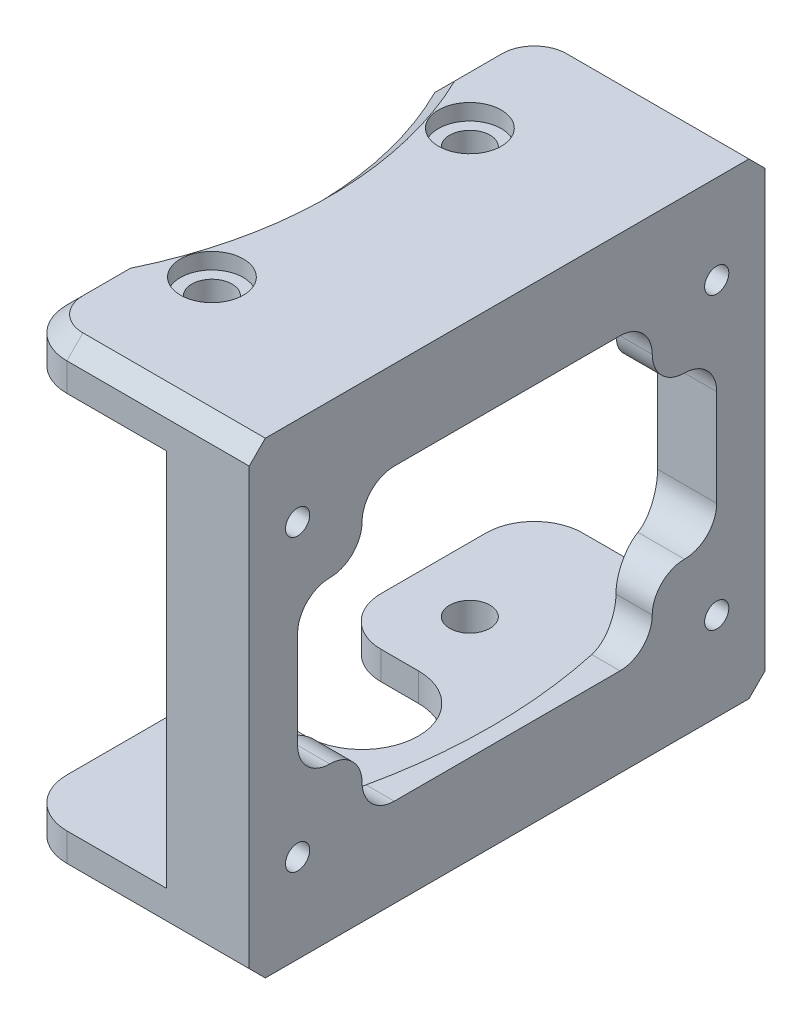
SolidWorks part; units mm, degrees
ref_plane "Спереди" through (0, 0, 0) normal (0, 0, 1) x (1, 0, 0)
ref_plane "Сверху" through (0, 0, 0) normal (0, 1, 0) x (1, 0, 0)
ref_plane "Справа" through (0, 0, 0) normal (1, 0, 0) x (0, 0, -1)
sketch "Эскиз1" plane through (0, 0, 0) normal (0, 1, 0) x (1, 0, 0)
  line L1 (19.6854, 16) -> (34, 16)
  line L2 (19.6854, 16) -> (19.6854, -16)
  line L3 (19.6854, -16) -> (34, -16)
  line L4 (34, 16) -> (34, -16)
  line L5 (19.6854, 16) -> (34, -16) construction
  line L6 (19.6854, -16) -> (34, 16) construction
  line L7 (23.6854, 8) -> (23.6854, -8) construction
  circle A0 centre (0, 0) radius 25 construction
  circle A1 centre (23.6854, 8) radius 1.25
  circle A2 centre (23.6854, -8) radius 1.25
  point P3 (26.8427, 0)
  dimension "D1" = 50
  dimension "D6" = 2.5
  dimension "D7" = 2.5
  dimension "D2" = 32
  dimension "D3" = 34
  dimension "D4" = 16
  dimension "D5" = 4
extrude "Бобышка-Вытянуть1" add sketch "Эскиз1" along normal mid plane 29
sketch "Эскиз2" plane through (0, 0, 0) normal (0, 1, 0) x (1, 0, 0)
  circle A0 centre (0, 0) radius 33
  dimension "D1" = 66
extrude "Вырез-Вытянуть1" cut sketch "Эскиз2" against normal mid plane 23.5
sketch "Эскиз3" plane through (34, 0, 0) normal (1, 0, 0) x (0, 0, -1)
  line L0 (-13, 5) -> (-9, 5)
  line L1 (13, 9) -> (-13, 9) construction
  line L2 (13, 9) -> (13, -9) construction
  line L3 (13, -9) -> (-13, -9) construction
  line L4 (-13, 9) -> (-13, -9) construction
  line L5 (13, 9) -> (-13, -9) construction
  line L6 (13, -9) -> (-13, 9) construction
  line L7 (-9, 5) -> (-9, 9)
  line L8 (-13, 0) -> (13, 0) construction
  line L9 (0, 9) -> (0, -9) construction
  line L10 (-9, -5) -> (-9, -9)
  line L11 (-13, -5) -> (-9, -5)
  line L12 (-13, 5) -> (-13, -5)
  line L13 (9, -5) -> (9, -9)
  line L14 (13, -5) -> (9, -5)
  line L15 (13, 5) -> (13, -5)
  line L16 (13, 5) -> (9, 5)
  line L17 (9, 5) -> (9, 9)
  line L18 (-9, 9) -> (9, 9)
  line L19 (9, -9) -> (-9, -9)
  circle A0 centre (-13, 9) radius 0.75
  circle A1 centre (-13, -9) radius 0.75
  circle A2 centre (13, 9) radius 0.75
  circle A3 centre (13, -9) radius 0.75
  point P0 (0, 0)
  dimension "D5" = 1.5
  dimension "D6" = 1.5
  dimension "D7" = 1.5
  dimension "D8" = 1.5
  dimension "D1" = 18
  dimension "D2" = 26
  dimension "D3" = 4
  dimension "D4" = 4
extrude "Вырез-Вытянуть2" cut sketch "Эскиз3" against normal through all
sketch "Эскиз4" plane through (0, -14.5, 0) normal (0, -1, 0) x (1, 0, 0)
  line L0 (19.6854, -16) -> (19.6854, 16) construction
  line L1 (25, 3.5) -> (19.6854, 3.5)
  line L2 (25, 3.5) -> (25, -3.5) construction
  line L3 (25, -3.5) -> (19.6854, -3.5)
  line L4 (19.6854, 3.5) -> (19.6854, -3.5)
  circle A0 centre (0, 0) radius 25 construction
  circle A1 centre (25, 0) radius 3.5
  line M9 (19.6854, 16) -> (19.6854, -16)
  dimension "D1" = 50
  dimension "D2" = 7
extrude "Вырез-Вытянуть3" cut sketch "Эскиз4" against normal up to next contours A1 L1 L3 M9 | A1 region at (21.0872, -14.5, 0) region at (25, -14.5, 0)
sketch "Эскиз6" plane through (0, 14.5, 0) normal (0, 1, 0) x (1, 0, 0)
  circle A0 centre (0, 0) radius 22
  dimension "D1" = 44
extrude "Вырез-Вытянуть5" cut sketch "Эскиз6" against normal up to next
fillet "Скругление1" radius 3 6 edges at (19.6854, -13.125, 3.5) (19.6854, -13.125, -3.5) (19.6854, -13.125, -16) (19.6854, 13.125, -16) (19.6854, 13.125, 16) (19.6854, -13.125, 16)
fillet "Скругление3" radius 2 12 edges at (32.1658, -5, 13) (32.8745, -5, 9) (32.8745, -9, 9) (32.8745, -9, -9) (32.8745, -5, -9) (32.1658, -5, -13) (32.1658, 5, -13) (32.8745, 5, -9) (32.8745, 9, -9) (32.1658, 5, 13) (32.8745, 9, 9) (32.8745, 5, 9)
chamfer "Фаска2" distance 1 angle 45 17 edges at (28.3427, -14.5, 16) (20.5641, -14.5, 15.1213) (19.6854, -14.5, 9.75) (20.5641, -14.5, 4.3787) (23.8427, -14.5, 3.5) (28.5, -14.5, 0) (23.8427, -14.5, -3.5) (20.5641, -14.5, -4.3787) (19.6854, -14.5, -9.75) (20.5641, -14.5, -15.1213) (28.3427, -14.5, -16) (28.3427, 14.5, 16) (20.5641, 14.5, 15.1213) (20.5641, 14.5, -15.1213) (28.3427, 14.5, -16) (22, 14.5, 0) (19.6854, 14.5, 11.4113)
sketch "Эскиз5" plane through (0, 14.5, 0) normal (0, 1, 0) x (1, 0, 0)
  circle A0 centre (23.6854, 8) radius 1.95
  circle A1 centre (23.6854, -8) radius 1.95
  dimension "D1" = 3.9
  dimension "D2" = 3.9
extrude "Вырез-Вытянуть4" cut sketch "Эскиз5" against normal blind 1
mirror "Зеркальное отражение1" about plane through (0, 0, 0) normal (0, 1, 0) of "Вырез-Вытянуть4"
equation "\"motor_diameter\"= 30"
equation "\"mm_diameter\"= IIF ( \"motor_diameter\" < 34 , 41 , \"motor_diameter\" + 8 )"
equation "\"upper_shafts_diameter\"= 5"
equation "\"upper_shats_length\"= 180"
equation "\"upper_bearing_d1\"= 10"
equation "\"upper_bearing_d2\"= 5"
equation "\"upper_bearing_h\"= 15"
equation "\"lower_shafts_diameter\"= 5"
equation "\"lower_shafts_length\"= 180"
equation "\"lower_bearing_d1\"= 10"
equation "\"lower_bearing_d2\"= 5"
equation "\"lower_bearing_h\"= 15"
equation "\"print_offset\"= 0.5"
equation "\"bh_screws_d\"= 2"
equation "\"bh_screws_h\"= 20"
equation "\"bh_screws_hh_d\"= 3.4"
equation "\"bh_screws_hh_h\"= 2"
equation "\"bh_nut_d\"= 3.8"
equation "\"bh_nut_h\"= 2"
equation "\"motor_screws_d\"= 3"
equation "\"motor_screws_h\"= 16"
equation "\"motor_screws_hh_d\"= 5.5"
equation "\"motor_screws_hh_h\"= 3"
equation "\"plate_hole_distance\"= 25.4"
equation "\"plate_screws_d\"= 6.5"
equation "\"shafts_diameter\"= IIF ( \"mm_diameter\" < 42 , 42 + 8 , \"mm_diameter\" + 8 )"
equation "\"central_hole_diameter\"= 8"
equation "\"bh_thikness\"= 4"
equation "\"ends_screws_d\"= 4"
equation "\"ends_screws_h\"= 16"
equation "\"ends_screws_hh_d\"= 6.7"
equation "\"ends_screws_hh_h\"= 4.1"
equation "\"ends_nut_d\"= 6.8"
equation "\"ends_nut_h\"= 3"
equation "\"system_radius\" = ( \"shafts_diameter\" + 12 + \"bh_thikness\" / 2 ) / 2"
equation "\"encoder_distance\"= \"system_radius\" + 4"
equation "\"tape_position\"= \"encoder_distance\" - 2 + 3.9 + 1.7 / 2"
equation "\"D1@Эскиз1\"=\"shafts_diameter\""
equation "\"D3@Эскиз1\"=\"encoder_distance\"-2"
equation "\"D5@Эскиз1\"=\"bh_thikness\""
equation "\"D6@Эскиз1\"=\"bh_screws_d\"+\"print_offset\""
equation "\"D7@Эскиз1\"=\"bh_screws_d\"+\"print_offset\""
equation "\"D1@Бобышка-Вытянуть1\"=\"upper_bearing_h\"+\"bh_thikness\"*2+6"
equation "\"D1@Эскиз2\"=\"system_radius\"*2+2"
equation "\"D1@Вырез-Вытянуть1\"=\"upper_bearing_h\"+\"bh_thikness\"*2+\"print_offset\""
equation "\"D5@Эскиз3\"=\"bh_screws_d\"-\"print_offset\""
equation "\"D6@Эскиз3\"=\"D5@Эскиз3\""
equation "\"D7@Эскиз3\"=\"D6@Эскиз3\""
equation "\"D8@Эскиз3\"=\"D5@Эскиз3\""
equation "\"D1@Эскиз4\"=\"shafts_diameter\""
equation "\"D2@Эскиз4\"=\"lower_shafts_diameter\"+2"
equation "\"D1@Эскиз5\"=\"bh_screws_hh_d\"+\"print_offset\""
equation "\"D2@Эскиз5\"=\"D1@Эскиз5\""
equation "\"D1@Эскиз6\"= IIF ( \"mm_diameter\" < 42 , 44 , \"mm_diameter\" + 2 )"
